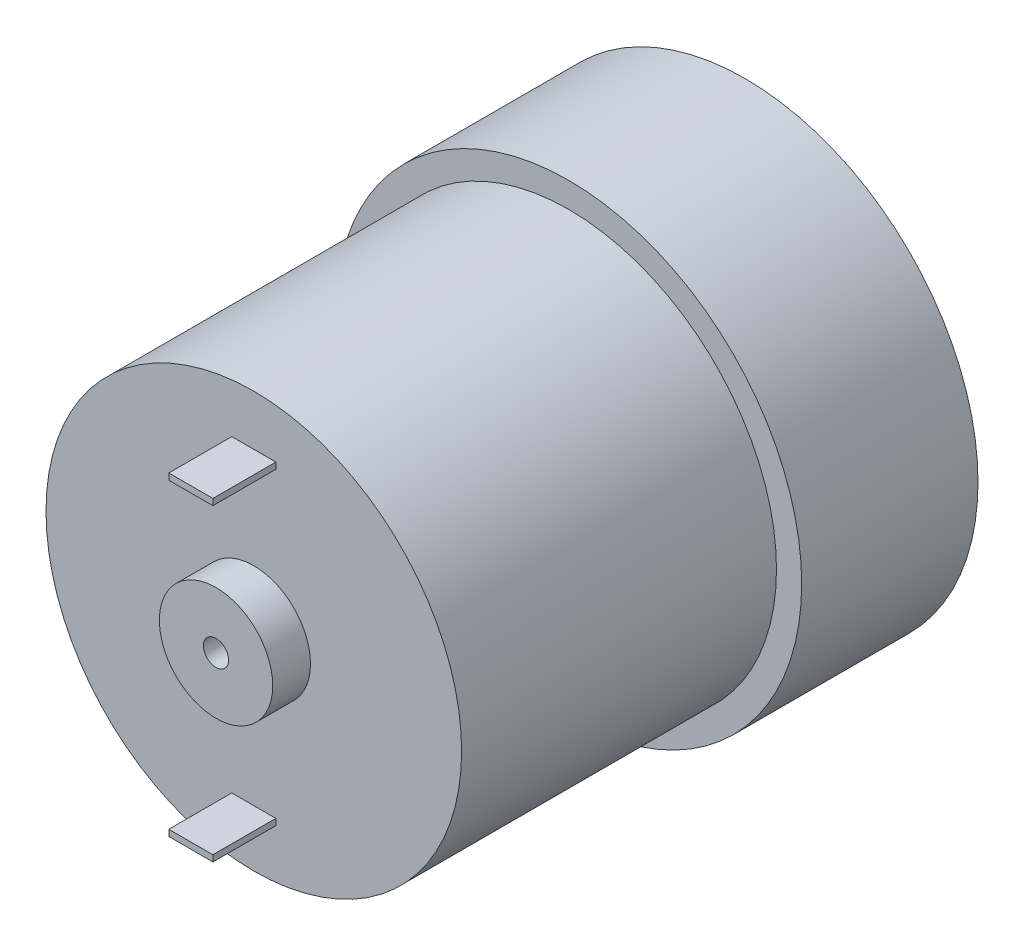
SolidWorks part; units mm, degrees
material "6063-O"
ref_plane "Front Plane" through (0, 0, 0) normal (0, 0, 1) x (1, 0, 0)
ref_plane "Top Plane" through (0, 0, 0) normal (0, 1, 0) x (1, 0, 0)
ref_plane "Right Plane" through (0, 0, 0) normal (1, 0, 0) x (0, 0, -1)
sketch "Sketch1" plane through (0, 0, 0) normal (0, 0, 1) x (1, 0, 0)
  circle A0 centre (0, 0) radius 18.5
  dimension "D1" = 37
extrude "Boss-Extrude1" add sketch "Sketch1" along normal blind 42
sketch "Sketch2" plane through (0, 0, 42) normal (0, 0, 1) x (1, 0, 0)
  circle A0 centre (0, 0) radius 18.5
  circle A1 centre (0, 0) radius 18.5 construction
  circle A2 centre (0, 0) radius 4.5
  dimension "D1" = 9
extrude "Cut-Extrude1" cut sketch "Sketch2" against normal blind 3
sketch "Sketch3" plane through (0, 0, 39) normal (0, 0, 1) x (1, 0, 0)
  circle A0 centre (0, 0) radius 18.5
  circle A1 centre (0, 0) radius 18.5 construction
  circle A2 centre (0, 0) radius 16.5
  circle M4 centre (0, 0) radius 18.5
  dimension "D1" = 33
extrude "Cut-Extrude4" cut sketch "Sketch3" against normal blind 25 contours A2 M4 region at (-17.9767, 0, 39)
sketch "Sketch4" plane through (0, 0, 0) normal (0, 0, -1) x (-1, 0, 0)
  line L0 (0, 0) -> (0, -18.5) construction
  circle A0 centre (0, 0) radius 18.5 construction
  circle A1 centre (0, -7) radius 6
  dimension "D2" = 12
  dimension "D1" = 7
extrude "Boss-Extrude2" add sketch "Sketch4" along normal blind 4.6
fillet "Fillet1" radius 0.5 1 edges at (-6, -7, -4.6)
sketch "Sketch5" plane through (0, 0, -4.6) normal (0, 0, -1) x (-1, 0, 0)
  circle A0 centre (0, -7) radius 3
  dimension "D1" = 6
extrude "Cut-Extrude5" cut sketch "Sketch5" against normal blind 10
sketch "Sketch6" plane through (0, 0, 42) normal (0, 0, 1) x (1, 0, 0)
  circle A0 centre (0, 0) radius 1
  dimension "D1" = 2
extrude "Cut-Extrude6" cut sketch "Sketch6" against normal blind 10
sketch "Sketch7" plane through (0, 0, 39) normal (0, 0, 1) x (1, 0, 0)
  line L0 (0, -16.5) -> (0, 16.5) construction
  line L2 (1.75, 12) -> (-1.75, 12)
  line L3 (1.75, 12) -> (1.75, 12.5)
  line L4 (1.75, 12.5) -> (-1.75, 12.5)
  line L5 (-1.75, 12) -> (-1.75, 12.5)
  line L6 (1.75, 12) -> (-1.75, 12.5) construction
  line L7 (1.75, 12.5) -> (-1.75, 12) construction
  line L8 (-1.75, -12) -> (1.75, -12)
  line L9 (-1.75, -12) -> (-1.75, -12.5)
  line L10 (-1.75, -12.5) -> (1.75, -12.5)
  line L11 (1.75, -12) -> (1.75, -12.5)
  line L12 (-1.75, -12) -> (1.75, -12.5) construction
  line L13 (-1.75, -12.5) -> (1.75, -12) construction
  circle A0 centre (0, 0) radius 16.5 construction
  point P5 (0, 12.25)
  point P10 (0, -12.25)
  dimension "D1" = 3.5
  dimension "D2" = 0.5
  dimension "D3" = 12
  dimension "D4" = 12
extrude "Boss-Extrude3" add sketch "Sketch7" along normal blind 5
sketch "Sketch8" plane through (0, 0, 0) normal (0, 0, -1) x (-1, 0, 0)
  line L0 (0, 0) -> (15.5, 0) construction
  line L1 (0, 0) -> (-15.5, 0) construction
  line L2 (0, 0) -> (-7.75, 13.4234) construction
  line L3 (0, 0) -> (-7.75, -13.4234) construction
  line L4 (-13.8293, -7) -> (13.8293, -7) construction
  circle A0 centre (0, 0) radius 15.5 construction
  circle A1 centre (-7.75, 13.4234) radius 1.5
  circle A2 centre (15.5, 0) radius 1.75
  circle A3 centre (-7.75, -13.4234) radius 1.5
  circle A4 centre (-13.8293, -7) radius 1.5
  circle A5 centre (-15.5, 0) radius 1.75
  circle A6 centre (13.8293, -7) radius 1.5
  circle A7 centre (0, 15.5) radius 1.75
  point P15 (0, -7)
  dimension "D1" = 31
  dimension "D4" = 3
  dimension "D5" = 3.5
  dimension "D2" = 120
  dimension "D3" = 120
hole_wizard "M3x0.5 Tapped Hole1" positions "Sketch9" profile "Sketch10" tap size "M3x0.5" standard "ANSI Metric"
sketch "Sketch9" plane through (0, 0, 0) normal (0, 0, -1) x (-1, 0, 0)
  point P0 (-7.75, 13.4234)
  point P3 (-13.8293, -7)
  point P6 (13.8293, -7)
  point P9 (-7.75, -13.4234)
sketch "Sketch10" plane through (7.75, 13.4234, 0) normal (1, 0, 0) x (0, 1, 0)
  line L0 (0, 0) -> (0, 8.2511)
  line L1 (0, 8.2511) -> (1.25, 7.5)
  line L2 (1.25, 7.5) -> (1.25, 0)
  line L5 (1.25, 0) -> (0, 0)
  line L10 (0, 8.2511) -> (-1.25, 7.5) construction
  line L11 (0, -6.35) -> (0, 107.95) construction
  dimension "Tap Drill Dia." = 2.5
  dimension "Tap Drill Depth" = 7.5
  dimension "Drill Angle" = 118
cosmetic thread "Hole Thread1" parameters "D1"=6, "D2"=3
cosmetic thread "Hole Thread2" parameters "D1"=6, "D2"=3
cosmetic thread "Hole Thread3" parameters "D1"=6, "D2"=3
cosmetic thread "Hole Thread4" parameters "D1"=6, "D2"=3
hole_wizard "Ø3.0mm Dowel Hole1" positions "Sketch11" profile "Sketch12" hole size "Ø3.0" standard "ANSI Metric"
sketch "Sketch11" plane through (0, 0, 0) normal (0, 0, -1) x (-1, 0, 0)
  point P0 (-15.5, 0)
  point P3 (0, 15.5)
  point P6 (15.5, 0)
sketch "Sketch12" plane through (15.5, 0, 0) normal (1, 0, 0) x (0, 1, 0)
  line L0 (0, 0) -> (0, 8.4013)
  line L1 (0, 8.4013) -> (1.5, 7.5)
  line L2 (1.5, 7.5) -> (1.5, 0)
  line L5 (1.5, 0) -> (0, 0)
  line L10 (0, 8.4013) -> (-1.5, 7.5) construction
  line L11 (0, -6.35) -> (0, 107.95) construction
  dimension "Hole Dia." = 3
  dimension "Hole Depth" = 7.5
  dimension "Drill Angle" = 118
equation "\"D4@Sketch7\"=\"D3@Sketch7\""
